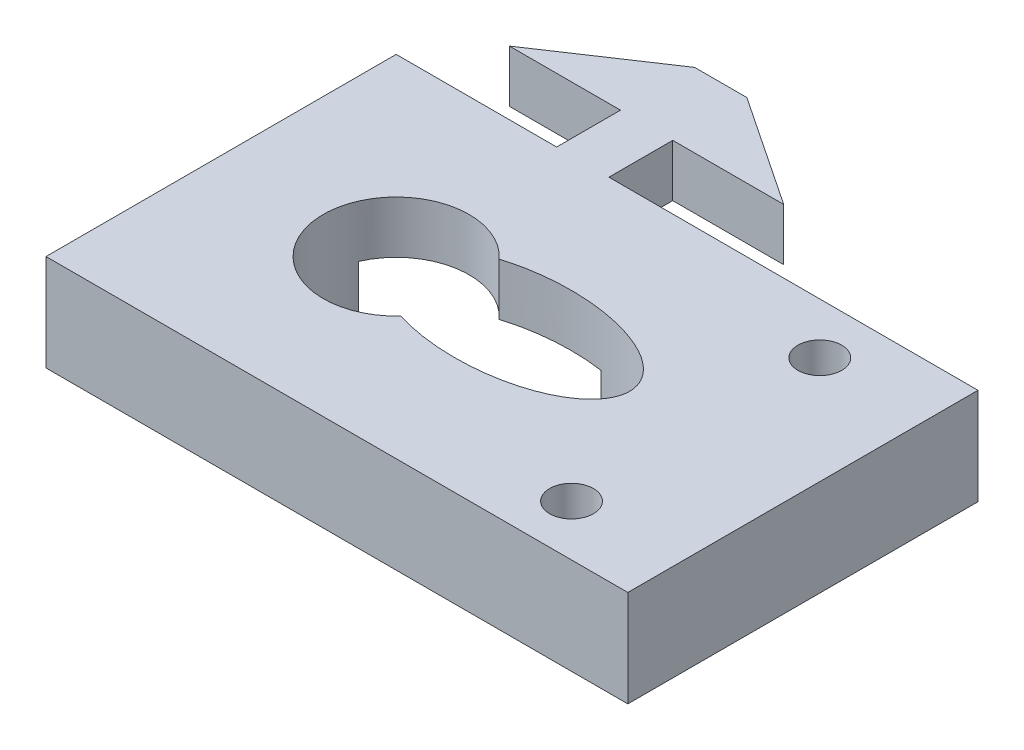
SolidWorks part; units mm, degrees
ref_plane "Front" through (0, 0, 0) normal (0, 0, 1) x (1, 0, 0)
ref_plane "Top" through (0, 0, 0) normal (0, 1, 0) x (1, 0, 0)
ref_plane "Right" through (0, 0, 0) normal (1, 0, 0) x (0, 0, -1)
sketch "Sketch1" plane through (0, 0, 0) normal (0, 1, 0) x (1, 0, 0)
  line L0 (-1.7907, 2.1875) -> (-9.398, 2.1875)
  line L2 (-1.7907, -2.1875) -> (-1.7907, 2.1875)
  line L4 (1.7907, -2.1875) -> (1.7907, 2.1875)
  line L7 (-9.398, 2.1875) -> (-1.7907, 7.2675)
  line L8 (-1.7907, 7.2675) -> (1.7907, 7.2675)
  line L9 (1.7907, 7.2675) -> (9.398, 2.1875)
  line L10 (9.398, 2.1875) -> (1.7907, 2.1875)
  line L11 (1.7907, -2.1875) -> (27.088, -2.1875)
  line L12 (-1.7907, -2.1875) -> (-12.79, -2.1875)
  line L13 (-12.79, -2.1875) -> (-12.79, -26.1875)
  line L14 (-12.79, -26.1875) -> (27.088, -26.1875)
  line L15 (27.088, -26.1875) -> (27.088, -2.1875)
  line L16 (27.088, -2.1875) -> (1.7907, -2.1875)
  point P0 (0, 0)
  point P17 (0, 7.2675)
  point P24 (1.7907, 0)
  dimension "D1" = 18.796
  dimension "D2" = 3.5814
  dimension "D3" = 39.878
  dimension "D4" = 24
  dimension "D5" = 5.08
  dimension "D6" = 12.79
  dimension "D7" = 4.375
extrude "Boss-Extrude1" add sketch "Sketch1" along normal blind 3.5814 contours L14 L15 L11 L4 L10 L9 L8 L7 L0 L2 L12 L13 region at (6.6455, 0, 12.9592)
ref_plane "Plane1" through (0, 1.7907, 0) normal (0, 1, 0) x (1, 0, 0)
sketch "Sketch7" plane through (0, 0, 0) normal (0, 1, 0) x (1, 0, 0)
  line L1 (-12.79, -2.1875) -> (27.088, -2.1875)
  line L2 (-12.79, -2.1875) -> (-12.79, -26.1875)
  line L3 (-12.79, -26.1875) -> (27.088, -26.1875)
  line L4 (27.088, -2.1875) -> (27.088, -26.1875)
extrude "Boss-Extrude2" add sketch "Sketch7" along normal blind 3.035 and the other way blind 3.035
sketch "Sketch5" plane through (0, 3.5814, 0) normal (0, 1, 0) x (1, 0, 0)
  line L0 (-12.79, -2.1875) -> (-12.79, -26.1875) construction
  line L1 (-12.79, -14.1875) -> (27.088, -14.1875) construction
  line L2 (27.088, -26.1875) -> (27.088, -2.1875) construction
  circle A0 centre (-0.79, -14.1875) radius 5
  circle A1 centre (19.738, -22.6965) radius 1.5
  circle A2 centre (19.738, -5.6785) radius 1.5
  ellipse E0 centre (7.21, -14.1875) end of major axis (-0.79, -14.1875) minor radius 4
  point P5 (-12.79, -14.1875)
  dimension "D2" = 10
  dimension "D6" = 3
  dimension "D1" = 12
  dimension "D3" = 8
  dimension "D4" = 16
  dimension "D5" = 17.018
  dimension "D7" = 7.35
extrude "Cut-Extrude3" cut sketch "Sketch5" against normal through all both and the other way through all contours A0 L1 E0 | E0 L1 A0 | A0 L1 E0 | L1 A0 E0 | L1 E0 A0 | L1 A0 E0 | A1 | A2 region at (1.9147, 3.5814, 12.8793) region at (-1.952, 3.5814, 16.6592) region at (1.9147, 3.5814, 15.4957) region at (-1.952, 3.5814, 11.7158) region at (8.8346, 3.5814, 12.3704) region at (8.8346, 3.5814, 16.0046) region at (19.738, 3.5814, 22.6965)
ref_plane "Plane2" through (0, 0, -17.2675) normal (0, 0, -1) x (-1, 0, 0)
sketch "Sketch8" plane through (0, 0, 2.1875) normal (0, 0, -1) x (-1, 0, 0)
  line L0 (-27.088, -3.035) -> (12.79, -3.035) construction
  line L1 (-9.398, 0) -> (9.398, 0)
  line L2 (-9.398, 0) -> (-9.398, -3.035)
  line L3 (-9.398, -3.035) -> (9.398, -3.035)
  line L4 (9.398, 0) -> (9.398, -3.035)
  line L5 (-9.398, 3.5814) -> (-9.398, 0) construction
  line L6 (9.398, 3.5814) -> (9.398, 0) construction
  line L7 (-1.7907, 0) -> (1.7907, 0) construction
extrude "Cut-Extrude4" cut sketch "Sketch8" against normal blind 10
